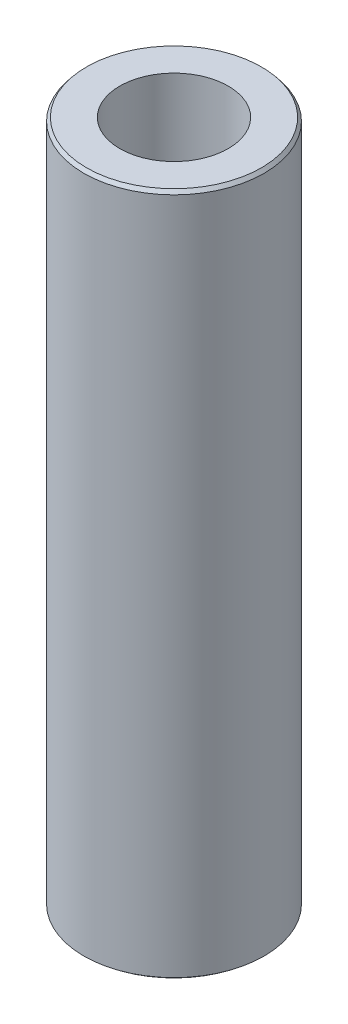
SolidWorks part; units mm, degrees
ref_plane "Front Plane" through (0, 0, 0) normal (0, 0, 1) x (1, 0, 0)
ref_plane "Top Plane" through (0, 0, 0) normal (0, 1, 0) x (1, 0, 0)
ref_plane "Right Plane" through (0, 0, 0) normal (1, 0, 0) x (0, 0, -1)
sketch "Sketch1" plane through (0, 0, 0) normal (0, 1, 0) x (1, 0, 0)
  circle A0 centre (0, 0) radius 15
  dimension "SHAFT_OD" = 30
extrude "Boss-Extrude1" add sketch "Sketch1" along normal blind 113.8188
sketch "Sketch2" plane through (0, 0, 0) normal (0, 1, 0) x (1, 0, 0)
  circle A0 centre (0, 0) radius 9.0225
  dimension "BORE_D" = 18.0451
extrude "Cut-Extrude1" cut sketch "Sketch2" along normal through all
chamfer "Chamfer1" distance 0.5679 angle 38.378 2 edges at (0, 113.8188, 15) (0, 0, 15) first distance on face at (0, 113.8188, 15) first distance on face at (0, 0, 9.0225)
